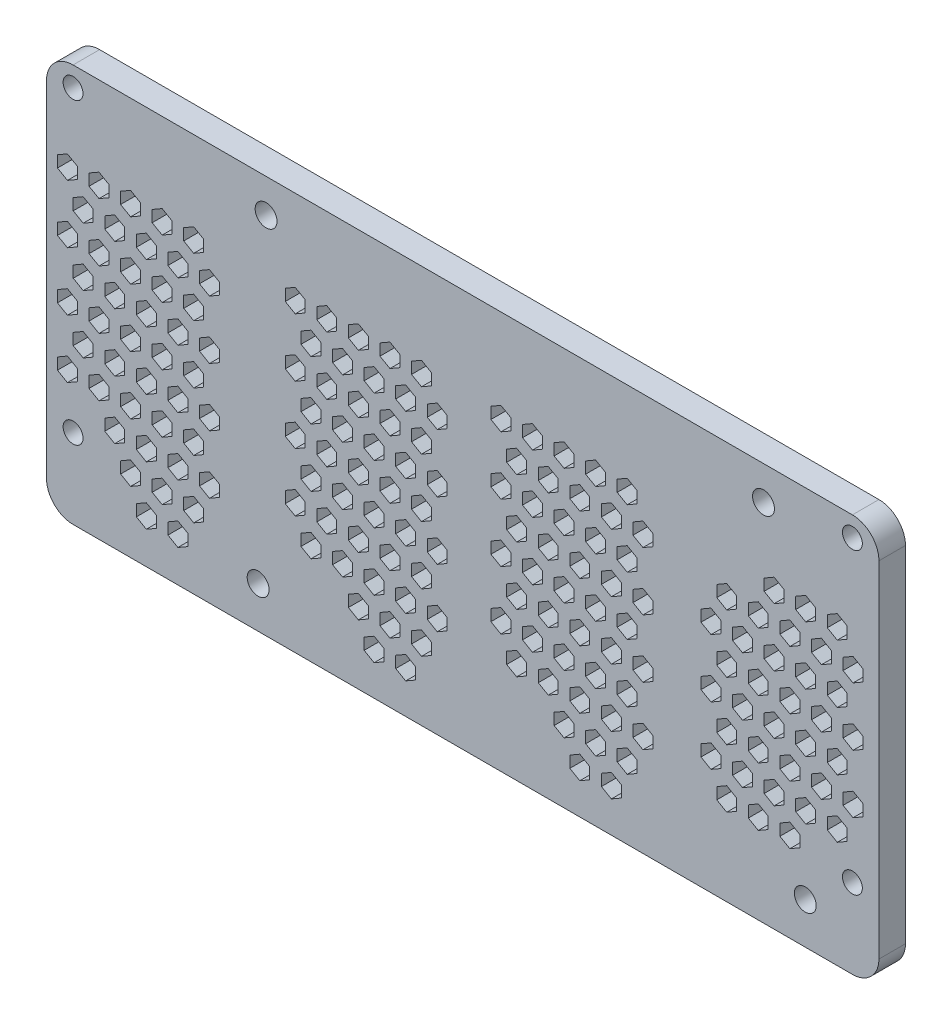
SolidWorks part; units mm, degrees
ref_plane "Front Plane" through (0, 0, 0) normal (0, 0, 1) x (1, 0, 0)
ref_plane "Top Plane" through (0, 0, 0) normal (0, 1, 0) x (1, 0, 0)
ref_plane "Right Plane" through (0, 0, 0) normal (1, 0, 0) x (0, 0, -1)
sketch "Sketch1" plane through (0, 0, 0) normal (0, 0, 1) x (1, 0, 0)
  line L1 (-44, 25.5882) -> (73.5, 25.5882)
  line L2 (-48, 21.5882) -> (-48, -30.4152)
  line L3 (-44, -34.4152) -> (73.5, -34.4152)
  line L4 (77.5, 21.5882) -> (77.5, -30.4152)
  line L10 (-44.8542, 13.5468) -> (-46.3542, 12.6808)
  line L11 (-46.3542, 12.6808) -> (-46.3542, 10.9488)
  line L12 (-46.3542, 10.9488) -> (-44.8542, 10.0827)
  line L13 (-44.8542, 10.0827) -> (-43.3542, 10.9488)
  line L14 (-43.3542, 10.9488) -> (-43.3542, 12.6808)
  line L15 (-43.3542, 12.6808) -> (-44.8542, 13.5468)
  line L17 (-42.4786, 9.1449) -> (-43.9786, 8.2789)
  line L18 (-43.9786, 8.2789) -> (-43.9786, 6.5468)
  line L19 (-43.9786, 6.5468) -> (-42.4786, 5.6808)
  line L20 (-42.4786, 5.6808) -> (-40.9786, 6.5468)
  line L21 (-40.9786, 6.5468) -> (-40.9786, 8.2789)
  line L22 (-40.9786, 8.2789) -> (-42.4786, 9.1449)
  line L23 (-40.0942, 13.5468) -> (-41.5942, 12.6808)
  line L24 (-41.5942, 12.6808) -> (-41.5942, 10.9488)
  line L25 (-41.5942, 10.9488) -> (-40.0942, 10.0827)
  line L26 (-40.0942, 10.0827) -> (-38.5942, 10.9488)
  line L27 (-38.5942, 10.9488) -> (-38.5942, 12.6808)
  line L28 (-38.5942, 12.6808) -> (-40.0942, 13.5468)
  line L29 (-37.7186, 9.1449) -> (-39.2186, 8.2789)
  line L30 (-39.2186, 8.2789) -> (-39.2186, 6.5468)
  line L31 (-39.2186, 6.5468) -> (-37.7186, 5.6808)
  line L32 (-37.7186, 5.6808) -> (-36.2186, 6.5468)
  line L33 (-36.2186, 6.5468) -> (-36.2186, 8.2789)
  line L34 (-36.2186, 8.2789) -> (-37.7186, 9.1449)
  line L35 (-35.3342, 13.5468) -> (-36.8342, 12.6808)
  line L36 (-36.8342, 12.6808) -> (-36.8342, 10.9488)
  line L37 (-36.8342, 10.9488) -> (-35.3342, 10.0827)
  line L38 (-35.3342, 10.0827) -> (-33.8342, 10.9488)
  line L39 (-33.8342, 10.9488) -> (-33.8342, 12.6808)
  line L40 (-33.8342, 12.6808) -> (-35.3342, 13.5468)
  line L41 (-32.9586, 9.1449) -> (-34.4586, 8.2789)
  line L42 (-34.4586, 8.2789) -> (-34.4586, 6.5468)
  line L43 (-34.4586, 6.5468) -> (-32.9586, 5.6808)
  line L44 (-32.9586, 5.6808) -> (-31.4586, 6.5468)
  line L45 (-31.4586, 6.5468) -> (-31.4586, 8.2789)
  line L46 (-31.4586, 8.2789) -> (-32.9586, 9.1449)
  line L47 (-30.5742, 13.5468) -> (-32.0742, 12.6808)
  line L48 (-32.0742, 12.6808) -> (-32.0742, 10.9488)
  line L49 (-32.0742, 10.9488) -> (-30.5742, 10.0827)
  line L50 (-30.5742, 10.0827) -> (-29.0742, 10.9488)
  line L51 (-29.0742, 10.9488) -> (-29.0742, 12.6808)
  line L52 (-29.0742, 12.6808) -> (-30.5742, 13.5468)
  line L53 (-28.1986, 9.1449) -> (-29.6986, 8.2789)
  line L54 (-29.6986, 8.2789) -> (-29.6986, 6.5468)
  line L55 (-29.6986, 6.5468) -> (-28.1986, 5.6808)
  line L56 (-28.1986, 5.6808) -> (-26.6986, 6.5468)
  line L57 (-26.6986, 6.5468) -> (-26.6986, 8.2789)
  line L58 (-26.6986, 8.2789) -> (-28.1986, 9.1449)
  line L59 (-25.8142, 13.5468) -> (-27.3142, 12.6808)
  line L60 (-27.3142, 12.6808) -> (-27.3142, 10.9488)
  line L61 (-27.3142, 10.9488) -> (-25.8142, 10.0827)
  line L62 (-25.8142, 10.0827) -> (-24.3142, 10.9488)
  line L63 (-24.3142, 10.9488) -> (-24.3142, 12.6808)
  line L64 (-24.3142, 12.6808) -> (-25.8142, 13.5468)
  line L65 (-23.4386, 9.1449) -> (-24.9386, 8.2789)
  line L66 (-24.9386, 8.2789) -> (-24.9386, 6.5468)
  line L67 (-24.9386, 6.5468) -> (-23.4386, 5.6808)
  line L68 (-23.4386, 5.6808) -> (-21.9386, 6.5468)
  line L69 (-21.9386, 6.5468) -> (-21.9386, 8.2789)
  line L70 (-21.9386, 8.2789) -> (-23.4386, 9.1449)
  line L71 (-40.0942, 4.7468) -> (-41.5942, 3.8808)
  line L72 (-41.5942, 3.8808) -> (-41.5942, 2.1488)
  line L73 (-41.5942, 2.1488) -> (-40.0942, 1.2827)
  line L74 (-40.0942, 1.2827) -> (-38.5942, 2.1488)
  line L75 (-38.5942, 2.1488) -> (-38.5942, 3.8808)
  line L76 (-38.5942, 3.8808) -> (-40.0942, 4.7468)
  line L77 (-37.7186, 0.3449) -> (-39.2186, -0.5211)
  line L78 (-39.2186, -0.5211) -> (-39.2186, -2.2532)
  line L79 (-39.2186, -2.2532) -> (-37.7186, -3.1192)
  line L80 (-37.7186, -3.1192) -> (-36.2186, -2.2532)
  line L81 (-36.2186, -2.2532) -> (-36.2186, -0.5211)
  line L82 (-36.2186, -0.5211) -> (-37.7186, 0.3449)
  line L83 (-35.3342, 4.7468) -> (-36.8342, 3.8808)
  line L84 (-36.8342, 3.8808) -> (-36.8342, 2.1488)
  line L85 (-36.8342, 2.1488) -> (-35.3342, 1.2827)
  line L86 (-35.3342, 1.2827) -> (-33.8342, 2.1488)
  line L87 (-33.8342, 2.1488) -> (-33.8342, 3.8808)
  line L88 (-33.8342, 3.8808) -> (-35.3342, 4.7468)
  line L89 (-32.9586, 0.3449) -> (-34.4586, -0.5211)
  line L90 (-34.4586, -0.5211) -> (-34.4586, -2.2532)
  line L91 (-34.4586, -2.2532) -> (-32.9586, -3.1192)
  line L92 (-32.9586, -3.1192) -> (-31.4586, -2.2532)
  line L93 (-31.4586, -2.2532) -> (-31.4586, -0.5211)
  line L94 (-31.4586, -0.5211) -> (-32.9586, 0.3449)
  line L95 (-30.5742, 4.7468) -> (-32.0742, 3.8808)
  line L96 (-32.0742, 3.8808) -> (-32.0742, 2.1488)
  line L97 (-32.0742, 2.1488) -> (-30.5742, 1.2827)
  line L98 (-30.5742, 1.2827) -> (-29.0742, 2.1488)
  line L99 (-29.0742, 2.1488) -> (-29.0742, 3.8808)
  line L100 (-29.0742, 3.8808) -> (-30.5742, 4.7468)
  line L101 (-28.1986, 0.3449) -> (-29.6986, -0.5211)
  line L102 (-29.6986, -0.5211) -> (-29.6986, -2.2532)
  line L103 (-29.6986, -2.2532) -> (-28.1986, -3.1192)
  line L104 (-28.1986, -3.1192) -> (-26.6986, -2.2532)
  line L105 (-26.6986, -2.2532) -> (-26.6986, -0.5211)
  line L106 (-26.6986, -0.5211) -> (-28.1986, 0.3449)
  line L107 (-25.8142, 4.7468) -> (-27.3142, 3.8808)
  line L108 (-27.3142, 3.8808) -> (-27.3142, 2.1488)
  line L109 (-27.3142, 2.1488) -> (-25.8142, 1.2827)
  line L110 (-25.8142, 1.2827) -> (-24.3142, 2.1488)
  line L111 (-24.3142, 2.1488) -> (-24.3142, 3.8808)
  line L112 (-24.3142, 3.8808) -> (-25.8142, 4.7468)
  line L113 (-23.4386, 0.3449) -> (-24.9386, -0.5211)
  line L114 (-24.9386, -0.5211) -> (-24.9386, -2.2532)
  line L115 (-24.9386, -2.2532) -> (-23.4386, -3.1192)
  line L116 (-23.4386, -3.1192) -> (-21.9386, -2.2532)
  line L117 (-21.9386, -2.2532) -> (-21.9386, -0.5211)
  line L118 (-21.9386, -0.5211) -> (-23.4386, 0.3449)
  line L119 (-40.0942, -4.0532) -> (-41.5942, -4.9192)
  line L120 (-41.5942, -4.9192) -> (-41.5942, -6.6512)
  line L121 (-41.5942, -6.6512) -> (-40.0942, -7.5173)
  line L122 (-40.0942, -7.5173) -> (-38.5942, -6.6512)
  line L123 (-38.5942, -6.6512) -> (-38.5942, -4.9192)
  line L124 (-38.5942, -4.9192) -> (-40.0942, -4.0532)
  line L125 (-37.7186, -8.4551) -> (-39.2186, -9.3211)
  line L126 (-39.2186, -9.3211) -> (-39.2186, -11.0532)
  line L127 (-39.2186, -11.0532) -> (-37.7186, -11.9192)
  line L128 (-37.7186, -11.9192) -> (-36.2186, -11.0532)
  line L129 (-36.2186, -11.0532) -> (-36.2186, -9.3211)
  line L130 (-36.2186, -9.3211) -> (-37.7186, -8.4551)
  line L131 (-35.3342, -4.0532) -> (-36.8342, -4.9192)
  line L132 (-36.8342, -4.9192) -> (-36.8342, -6.6512)
  line L133 (-36.8342, -6.6512) -> (-35.3342, -7.5173)
  line L134 (-35.3342, -7.5173) -> (-33.8342, -6.6512)
  line L135 (-33.8342, -6.6512) -> (-33.8342, -4.9192)
  line L136 (-33.8342, -4.9192) -> (-35.3342, -4.0532)
  line L137 (-32.9586, -8.4551) -> (-34.4586, -9.3211)
  line L138 (-34.4586, -9.3211) -> (-34.4586, -11.0532)
  line L139 (-34.4586, -11.0532) -> (-32.9586, -11.9192)
  line L140 (-32.9586, -11.9192) -> (-31.4586, -11.0532)
  line L141 (-31.4586, -11.0532) -> (-31.4586, -9.3211)
  line L142 (-31.4586, -9.3211) -> (-32.9586, -8.4551)
  line L143 (-30.5742, -4.0532) -> (-32.0742, -4.9192)
  line L144 (-32.0742, -4.9192) -> (-32.0742, -6.6512)
  line L145 (-32.0742, -6.6512) -> (-30.5742, -7.5173)
  line L146 (-30.5742, -7.5173) -> (-29.0742, -6.6512)
  line L147 (-29.0742, -6.6512) -> (-29.0742, -4.9192)
  line L148 (-29.0742, -4.9192) -> (-30.5742, -4.0532)
  line L149 (-28.1986, -8.4551) -> (-29.6986, -9.3211)
  line L150 (-29.6986, -9.3211) -> (-29.6986, -11.0532)
  line L151 (-29.6986, -11.0532) -> (-28.1986, -11.9192)
  line L152 (-28.1986, -11.9192) -> (-26.6986, -11.0532)
  line L153 (-26.6986, -11.0532) -> (-26.6986, -9.3211)
  line L154 (-26.6986, -9.3211) -> (-28.1986, -8.4551)
  line L155 (-25.8142, -4.0532) -> (-27.3142, -4.9192)
  line L156 (-27.3142, -4.9192) -> (-27.3142, -6.6512)
  line L157 (-27.3142, -6.6512) -> (-25.8142, -7.5173)
  line L158 (-25.8142, -7.5173) -> (-24.3142, -6.6512)
  line L159 (-24.3142, -6.6512) -> (-24.3142, -4.9192)
  line L160 (-24.3142, -4.9192) -> (-25.8142, -4.0532)
  line L161 (-23.4386, -8.4551) -> (-24.9386, -9.3211)
  line L162 (-24.9386, -9.3211) -> (-24.9386, -11.0532)
  line L163 (-24.9386, -11.0532) -> (-23.4386, -11.9192)
  line L164 (-23.4386, -11.9192) -> (-21.9386, -11.0532)
  line L165 (-21.9386, -11.0532) -> (-21.9386, -9.3211)
  line L166 (-21.9386, -9.3211) -> (-23.4386, -8.4551)
  line L167 (-40.0942, -12.8532) -> (-41.5942, -13.7192)
  line L168 (-41.5942, -13.7192) -> (-41.5942, -15.4512)
  line L169 (-41.5942, -15.4512) -> (-40.0942, -16.3173)
  line L170 (-40.0942, -16.3173) -> (-38.5942, -15.4512)
  line L171 (-38.5942, -15.4512) -> (-38.5942, -13.7192)
  line L172 (-38.5942, -13.7192) -> (-40.0942, -12.8532)
  line L173 (-37.7186, -17.2551) -> (-39.2186, -18.1211)
  line L174 (-39.2186, -18.1211) -> (-39.2186, -19.8532)
  line L175 (-39.2186, -19.8532) -> (-37.7186, -20.7192)
  line L176 (-37.7186, -20.7192) -> (-36.2186, -19.8532)
  line L177 (-36.2186, -19.8532) -> (-36.2186, -18.1211)
  line L178 (-36.2186, -18.1211) -> (-37.7186, -17.2551)
  line L179 (-35.3342, -12.8532) -> (-36.8342, -13.7192)
  line L180 (-36.8342, -13.7192) -> (-36.8342, -15.4512)
  line L181 (-36.8342, -15.4512) -> (-35.3342, -16.3173)
  line L182 (-35.3342, -16.3173) -> (-33.8342, -15.4512)
  line L183 (-33.8342, -15.4512) -> (-33.8342, -13.7192)
  line L184 (-33.8342, -13.7192) -> (-35.3342, -12.8532)
  line L185 (-32.9586, -17.2551) -> (-34.4586, -18.1211)
  line L186 (-34.4586, -18.1211) -> (-34.4586, -19.8532)
  line L187 (-34.4586, -19.8532) -> (-32.9586, -20.7192)
  line L188 (-32.9586, -20.7192) -> (-31.4586, -19.8532)
  line L189 (-31.4586, -19.8532) -> (-31.4586, -18.1211)
  line L190 (-31.4586, -18.1211) -> (-32.9586, -17.2551)
  line L191 (-30.5742, -12.8532) -> (-32.0742, -13.7192)
  line L192 (-32.0742, -13.7192) -> (-32.0742, -15.4512)
  line L193 (-32.0742, -15.4512) -> (-30.5742, -16.3173)
  line L194 (-30.5742, -16.3173) -> (-29.0742, -15.4512)
  line L195 (-29.0742, -15.4512) -> (-29.0742, -13.7192)
  line L196 (-29.0742, -13.7192) -> (-30.5742, -12.8532)
  line L197 (-28.1986, -17.2551) -> (-29.6986, -18.1211)
  line L198 (-29.6986, -18.1211) -> (-29.6986, -19.8532)
  line L199 (-29.6986, -19.8532) -> (-28.1986, -20.7192)
  line L200 (-28.1986, -20.7192) -> (-26.6986, -19.8532)
  line L201 (-26.6986, -19.8532) -> (-26.6986, -18.1211)
  line L202 (-26.6986, -18.1211) -> (-28.1986, -17.2551)
  line L203 (-25.8142, -12.8532) -> (-27.3142, -13.7192)
  line L204 (-27.3142, -13.7192) -> (-27.3142, -15.4512)
  line L205 (-27.3142, -15.4512) -> (-25.8142, -16.3173)
  line L206 (-25.8142, -16.3173) -> (-24.3142, -15.4512)
  line L207 (-24.3142, -15.4512) -> (-24.3142, -13.7192)
  line L208 (-24.3142, -13.7192) -> (-25.8142, -12.8532)
  line L209 (-23.4386, -17.2551) -> (-24.9386, -18.1211)
  line L210 (-24.9386, -18.1211) -> (-24.9386, -19.8532)
  line L211 (-24.9386, -19.8532) -> (-23.4386, -20.7192)
  line L212 (-23.4386, -20.7192) -> (-21.9386, -19.8532)
  line L213 (-21.9386, -19.8532) -> (-21.9386, -18.1211)
  line L214 (-21.9386, -18.1211) -> (-23.4386, -17.2551)
  line L227 (-35.3342, -21.6532) -> (-36.8342, -22.5192)
  line L228 (-36.8342, -22.5192) -> (-36.8342, -24.2512)
  line L229 (-36.8342, -24.2512) -> (-35.3342, -25.1173)
  line L230 (-35.3342, -25.1173) -> (-33.8342, -24.2512)
  line L231 (-33.8342, -24.2512) -> (-33.8342, -22.5192)
  line L232 (-33.8342, -22.5192) -> (-35.3342, -21.6532)
  line L233 (-32.9586, -26.0551) -> (-34.4586, -26.9211)
  line L234 (-34.4586, -26.9211) -> (-34.4586, -28.6532)
  line L235 (-34.4586, -28.6532) -> (-32.9586, -29.5192)
  line L236 (-32.9586, -29.5192) -> (-31.4586, -28.6532)
  line L237 (-31.4586, -28.6532) -> (-31.4586, -26.9211)
  line L238 (-31.4586, -26.9211) -> (-32.9586, -26.0551)
  line L239 (-30.5742, -21.6532) -> (-32.0742, -22.5192)
  line L240 (-32.0742, -22.5192) -> (-32.0742, -24.2512)
  line L241 (-32.0742, -24.2512) -> (-30.5742, -25.1173)
  line L242 (-30.5742, -25.1173) -> (-29.0742, -24.2512)
  line L243 (-29.0742, -24.2512) -> (-29.0742, -22.5192)
  line L244 (-29.0742, -22.5192) -> (-30.5742, -21.6532)
  line L245 (-28.1986, -26.0551) -> (-29.6986, -26.9211)
  line L246 (-29.6986, -26.9211) -> (-29.6986, -28.6532)
  line L247 (-29.6986, -28.6532) -> (-28.1986, -29.5192)
  line L248 (-28.1986, -29.5192) -> (-26.6986, -28.6532)
  line L249 (-26.6986, -28.6532) -> (-26.6986, -26.9211)
  line L250 (-26.6986, -26.9211) -> (-28.1986, -26.0551)
  line L251 (-25.8142, -21.6532) -> (-27.3142, -22.5192)
  line L252 (-27.3142, -22.5192) -> (-27.3142, -24.2512)
  line L253 (-27.3142, -24.2512) -> (-25.8142, -25.1173)
  line L254 (-25.8142, -25.1173) -> (-24.3142, -24.2512)
  line L255 (-24.3142, -24.2512) -> (-24.3142, -22.5192)
  line L256 (-24.3142, -22.5192) -> (-25.8142, -21.6532)
  line L263 (-44.8542, 4.7468) -> (-46.3542, 3.8808)
  line L264 (-46.3542, 3.8808) -> (-46.3542, 2.1488)
  line L265 (-46.3542, 2.1488) -> (-44.8542, 1.2827)
  line L266 (-44.8542, 1.2827) -> (-43.3542, 2.1488)
  line L267 (-43.3542, 2.1488) -> (-43.3542, 3.8808)
  line L268 (-43.3542, 3.8808) -> (-44.8542, 4.7468)
  line L269 (-42.4786, 0.3449) -> (-43.9786, -0.5211)
  line L270 (-43.9786, -0.5211) -> (-43.9786, -2.2532)
  line L271 (-43.9786, -2.2532) -> (-42.4786, -3.1192)
  line L272 (-42.4786, -3.1192) -> (-40.9786, -2.2532)
  line L273 (-40.9786, -2.2532) -> (-40.9786, -0.5211)
  line L274 (-40.9786, -0.5211) -> (-42.4786, 0.3449)
  line L275 (-44.8542, -4.0532) -> (-46.3542, -4.9192)
  line L276 (-46.3542, -4.9192) -> (-46.3542, -6.6512)
  line L277 (-46.3542, -6.6512) -> (-44.8542, -7.5173)
  line L278 (-44.8542, -7.5173) -> (-43.3542, -6.6512)
  line L279 (-43.3542, -6.6512) -> (-43.3542, -4.9192)
  line L280 (-43.3542, -4.9192) -> (-44.8542, -4.0532)
  line L281 (-42.4786, -8.4551) -> (-43.9786, -9.3211)
  line L282 (-43.9786, -9.3211) -> (-43.9786, -11.0532)
  line L283 (-43.9786, -11.0532) -> (-42.4786, -11.9192)
  line L284 (-42.4786, -11.9192) -> (-40.9786, -11.0532)
  line L285 (-40.9786, -11.0532) -> (-40.9786, -9.3211)
  line L286 (-40.9786, -9.3211) -> (-42.4786, -8.4551)
  line L287 (-44.8542, -12.8532) -> (-46.3542, -13.7192)
  line L288 (-46.3542, -13.7192) -> (-46.3542, -15.4512)
  line L289 (-46.3542, -15.4512) -> (-44.8542, -16.3173)
  line L290 (-44.8542, -16.3173) -> (-43.3542, -15.4512)
  line L291 (-43.3542, -15.4512) -> (-43.3542, -13.7192)
  line L292 (-43.3542, -13.7192) -> (-44.8542, -12.8532)
  line L311 (-44.8542, -21.6532) -> (-46.3542, -22.5192) [skipped]
  line L312 (-46.3542, -22.5192) -> (-46.3542, -24.2512) [skipped]
  line L313 (-46.3542, -24.2512) -> (-44.8542, -25.1173) [skipped]
  line L314 (-44.8542, -25.1173) -> (-43.3542, -24.2512) [skipped]
  line L315 (-43.3542, -24.2512) -> (-43.3542, -22.5192) [skipped]
  line L316 (-43.3542, -22.5192) -> (-44.8542, -21.6532) [skipped]
  line L317 (-42.4786, -26.0551) -> (-43.9786, -26.9211) [skipped]
  line L318 (-43.9786, -26.9211) -> (-43.9786, -28.6532) [skipped]
  line L319 (-43.9786, -28.6532) -> (-42.4786, -29.5192) [skipped]
  line L320 (-42.4786, -29.5192) -> (-40.9786, -28.6532) [skipped]
  line L321 (-40.9786, -28.6532) -> (-40.9786, -26.9211) [skipped]
  line L322 (-40.9786, -26.9211) -> (-42.4786, -26.0551) [skipped]
  line L323 (-37.7186, -26.0551) -> (-39.2186, -26.9211) [skipped]
  line L324 (-39.2186, -26.9211) -> (-39.2186, -28.6532) [skipped]
  line L325 (-39.2186, -28.6532) -> (-37.7186, -29.5192) [skipped]
  line L326 (-37.7186, -29.5192) -> (-36.2186, -28.6532) [skipped]
  line L327 (-36.2186, -28.6532) -> (-36.2186, -26.9211) [skipped]
  line L328 (-36.2186, -26.9211) -> (-37.7186, -26.0551) [skipped]
  line L329 (-40.0942, -21.6532) -> (-41.5942, -22.5192) [skipped]
  line L330 (-41.5942, -22.5192) -> (-41.5942, -24.2512) [skipped]
  line L331 (-41.5942, -24.2512) -> (-40.0942, -25.1173) [skipped]
  line L332 (-40.0942, -25.1173) -> (-38.5942, -24.2512) [skipped]
  line L333 (-38.5942, -24.2512) -> (-38.5942, -22.5192) [skipped]
  line L334 (-38.5942, -22.5192) -> (-40.0942, -21.6532) [skipped]
  line L335 (-23.4386, -26.0551) -> (-24.9386, -26.9211) [skipped]
  line L336 (-24.9386, -26.9211) -> (-24.9386, -28.6532) [skipped]
  line L337 (-24.9386, -28.6532) -> (-23.4386, -29.5192) [skipped]
  line L338 (-23.4386, -29.5192) -> (-21.9386, -28.6532) [skipped]
  line L339 (-21.9386, -28.6532) -> (-21.9386, -26.9211) [skipped]
  line L340 (-21.9386, -26.9211) -> (-23.4386, -26.0551) [skipped]
  line L347 (54.5534, 7.152) -> (53.0534, 6.286)
  line L348 (53.0534, 6.286) -> (53.0534, 4.554)
  line L349 (53.0534, 4.554) -> (54.5534, 3.6879)
  line L350 (54.5534, 3.6879) -> (56.0534, 4.554)
  line L351 (56.0534, 4.554) -> (56.0534, 6.286)
  line L352 (56.0534, 6.286) -> (54.5534, 7.152)
  line L359 (59.3134, 7.152) -> (57.8134, 6.286)
  line L360 (57.8134, 6.286) -> (57.8134, 4.554)
  line L361 (57.8134, 4.554) -> (59.3134, 3.6879)
  line L362 (59.3134, 3.6879) -> (60.8134, 4.554)
  line L363 (60.8134, 4.554) -> (60.8134, 6.286)
  line L364 (60.8134, 6.286) -> (59.3134, 7.152)
  line L365 (61.6978, 11.554) -> (60.1978, 10.6879)
  line L366 (60.1978, 10.6879) -> (60.1978, 8.9559)
  line L367 (60.1978, 8.9559) -> (61.6978, 8.0899)
  line L368 (61.6978, 8.0899) -> (63.1978, 8.9559)
  line L369 (63.1978, 8.9559) -> (63.1978, 10.6879)
  line L370 (63.1978, 10.6879) -> (61.6978, 11.554)
  line L371 (64.0734, 7.152) -> (62.5734, 6.286)
  line L372 (62.5734, 6.286) -> (62.5734, 4.554)
  line L373 (62.5734, 4.554) -> (64.0734, 3.6879)
  line L374 (64.0734, 3.6879) -> (65.5734, 4.554)
  line L375 (65.5734, 4.554) -> (65.5734, 6.286)
  line L376 (65.5734, 6.286) -> (64.0734, 7.152)
  line L377 (66.4578, 11.554) -> (64.9578, 10.6879)
  line L378 (64.9578, 10.6879) -> (64.9578, 8.9559)
  line L379 (64.9578, 8.9559) -> (66.4578, 8.0899)
  line L380 (66.4578, 8.0899) -> (67.9578, 8.9559)
  line L381 (67.9578, 8.9559) -> (67.9578, 10.6879)
  line L382 (67.9578, 10.6879) -> (66.4578, 11.554)
  line L383 (68.8334, 7.152) -> (67.3334, 6.286)
  line L384 (67.3334, 6.286) -> (67.3334, 4.554)
  line L385 (67.3334, 4.554) -> (68.8334, 3.6879)
  line L386 (68.8334, 3.6879) -> (70.3334, 4.554)
  line L387 (70.3334, 4.554) -> (70.3334, 6.286)
  line L388 (70.3334, 6.286) -> (68.8334, 7.152)
  line L389 (71.2178, 11.554) -> (69.7178, 10.6879)
  line L390 (69.7178, 10.6879) -> (69.7178, 8.9559)
  line L391 (69.7178, 8.9559) -> (71.2178, 8.0899)
  line L392 (71.2178, 8.0899) -> (72.7178, 8.9559)
  line L393 (72.7178, 8.9559) -> (72.7178, 10.6879)
  line L394 (72.7178, 10.6879) -> (71.2178, 11.554)
  line L395 (73.5934, 7.152) -> (72.0934, 6.286)
  line L396 (72.0934, 6.286) -> (72.0934, 4.554)
  line L397 (72.0934, 4.554) -> (73.5934, 3.6879)
  line L398 (73.5934, 3.6879) -> (75.0934, 4.554)
  line L399 (75.0934, 4.554) -> (75.0934, 6.286)
  line L400 (75.0934, 6.286) -> (73.5934, 7.152)
  line L401 (56.9378, 2.754) -> (55.4378, 1.8879)
  line L402 (55.4378, 1.8879) -> (55.4378, 0.1559)
  line L403 (55.4378, 0.1559) -> (56.9378, -0.7101)
  line L404 (56.9378, -0.7101) -> (58.4378, 0.1559)
  line L405 (58.4378, 0.1559) -> (58.4378, 1.8879)
  line L406 (58.4378, 1.8879) -> (56.9378, 2.754)
  line L407 (59.3134, -1.648) -> (57.8134, -2.514)
  line L408 (57.8134, -2.514) -> (57.8134, -4.246)
  line L409 (57.8134, -4.246) -> (59.3134, -5.1121)
  line L410 (59.3134, -5.1121) -> (60.8134, -4.246)
  line L411 (60.8134, -4.246) -> (60.8134, -2.514)
  line L412 (60.8134, -2.514) -> (59.3134, -1.648)
  line L413 (61.6978, 2.754) -> (60.1978, 1.8879)
  line L414 (60.1978, 1.8879) -> (60.1978, 0.1559)
  line L415 (60.1978, 0.1559) -> (61.6978, -0.7101)
  line L416 (61.6978, -0.7101) -> (63.1978, 0.1559)
  line L417 (63.1978, 0.1559) -> (63.1978, 1.8879)
  line L418 (63.1978, 1.8879) -> (61.6978, 2.754)
  line L419 (64.0734, -1.648) -> (62.5734, -2.514)
  line L420 (62.5734, -2.514) -> (62.5734, -4.246)
  line L421 (62.5734, -4.246) -> (64.0734, -5.1121)
  line L422 (64.0734, -5.1121) -> (65.5734, -4.246)
  line L423 (65.5734, -4.246) -> (65.5734, -2.514)
  line L424 (65.5734, -2.514) -> (64.0734, -1.648)
  line L425 (66.4578, 2.754) -> (64.9578, 1.8879)
  line L426 (64.9578, 1.8879) -> (64.9578, 0.1559)
  line L427 (64.9578, 0.1559) -> (66.4578, -0.7101)
  line L428 (66.4578, -0.7101) -> (67.9578, 0.1559)
  line L429 (67.9578, 0.1559) -> (67.9578, 1.8879)
  line L430 (67.9578, 1.8879) -> (66.4578, 2.754)
  line L431 (68.8334, -1.648) -> (67.3334, -2.514)
  line L432 (67.3334, -2.514) -> (67.3334, -4.246)
  line L433 (67.3334, -4.246) -> (68.8334, -5.1121)
  line L434 (68.8334, -5.1121) -> (70.3334, -4.246)
  line L435 (70.3334, -4.246) -> (70.3334, -2.514)
  line L436 (70.3334, -2.514) -> (68.8334, -1.648)
  line L437 (71.2178, 2.754) -> (69.7178, 1.8879)
  line L438 (69.7178, 1.8879) -> (69.7178, 0.1559)
  line L439 (69.7178, 0.1559) -> (71.2178, -0.7101)
  line L440 (71.2178, -0.7101) -> (72.7178, 0.1559)
  line L441 (72.7178, 0.1559) -> (72.7178, 1.8879)
  line L442 (72.7178, 1.8879) -> (71.2178, 2.754)
  line L443 (73.5934, -1.648) -> (72.0934, -2.514)
  line L444 (72.0934, -2.514) -> (72.0934, -4.246)
  line L445 (72.0934, -4.246) -> (73.5934, -5.1121)
  line L446 (73.5934, -5.1121) -> (75.0934, -4.246)
  line L447 (75.0934, -4.246) -> (75.0934, -2.514)
  line L448 (75.0934, -2.514) -> (73.5934, -1.648)
  line L449 (56.9378, -6.046) -> (55.4378, -6.9121)
  line L450 (55.4378, -6.9121) -> (55.4378, -8.6441)
  line L451 (55.4378, -8.6441) -> (56.9378, -9.5101)
  line L452 (56.9378, -9.5101) -> (58.4378, -8.6441)
  line L453 (58.4378, -8.6441) -> (58.4378, -6.9121)
  line L454 (58.4378, -6.9121) -> (56.9378, -6.046)
  line L455 (59.3134, -10.448) -> (57.8134, -11.314)
  line L456 (57.8134, -11.314) -> (57.8134, -13.046)
  line L457 (57.8134, -13.046) -> (59.3134, -13.9121)
  line L458 (59.3134, -13.9121) -> (60.8134, -13.046)
  line L459 (60.8134, -13.046) -> (60.8134, -11.314)
  line L460 (60.8134, -11.314) -> (59.3134, -10.448)
  line L461 (61.6978, -6.046) -> (60.1978, -6.9121)
  line L462 (60.1978, -6.9121) -> (60.1978, -8.6441)
  line L463 (60.1978, -8.6441) -> (61.6978, -9.5101)
  line L464 (61.6978, -9.5101) -> (63.1978, -8.6441)
  line L465 (63.1978, -8.6441) -> (63.1978, -6.9121)
  line L466 (63.1978, -6.9121) -> (61.6978, -6.046)
  line L467 (64.0734, -10.448) -> (62.5734, -11.314)
  line L468 (62.5734, -11.314) -> (62.5734, -13.046)
  line L469 (62.5734, -13.046) -> (64.0734, -13.9121)
  line L470 (64.0734, -13.9121) -> (65.5734, -13.046)
  line L471 (65.5734, -13.046) -> (65.5734, -11.314)
  line L472 (65.5734, -11.314) -> (64.0734, -10.448)
  line L473 (66.4578, -6.046) -> (64.9578, -6.9121)
  line L474 (64.9578, -6.9121) -> (64.9578, -8.6441)
  line L475 (64.9578, -8.6441) -> (66.4578, -9.5101)
  line L476 (66.4578, -9.5101) -> (67.9578, -8.6441)
  line L477 (67.9578, -8.6441) -> (67.9578, -6.9121)
  line L478 (67.9578, -6.9121) -> (66.4578, -6.046)
  line L479 (68.8334, -10.448) -> (67.3334, -11.314)
  line L480 (67.3334, -11.314) -> (67.3334, -13.046)
  line L481 (67.3334, -13.046) -> (68.8334, -13.9121)
  line L482 (68.8334, -13.9121) -> (70.3334, -13.046)
  line L483 (70.3334, -13.046) -> (70.3334, -11.314)
  line L484 (70.3334, -11.314) -> (68.8334, -10.448)
  line L485 (71.2178, -6.046) -> (69.7178, -6.9121)
  line L486 (69.7178, -6.9121) -> (69.7178, -8.6441)
  line L487 (69.7178, -8.6441) -> (71.2178, -9.5101)
  line L488 (71.2178, -9.5101) -> (72.7178, -8.6441)
  line L489 (72.7178, -8.6441) -> (72.7178, -6.9121)
  line L490 (72.7178, -6.9121) -> (71.2178, -6.046)
  line L491 (73.5934, -10.448) -> (72.0934, -11.314)
  line L492 (72.0934, -11.314) -> (72.0934, -13.046)
  line L493 (72.0934, -13.046) -> (73.5934, -13.9121)
  line L494 (73.5934, -13.9121) -> (75.0934, -13.046)
  line L495 (75.0934, -13.046) -> (75.0934, -11.314)
  line L496 (75.0934, -11.314) -> (73.5934, -10.448)
  line L497 (56.9378, -14.846) -> (55.4378, -15.7121)
  line L498 (55.4378, -15.7121) -> (55.4378, -17.4441)
  line L499 (55.4378, -17.4441) -> (56.9378, -18.3101)
  line L500 (56.9378, -18.3101) -> (58.4378, -17.4441)
  line L501 (58.4378, -17.4441) -> (58.4378, -15.7121)
  line L502 (58.4378, -15.7121) -> (56.9378, -14.846)
  line L503 (59.3134, -19.248) -> (57.8134, -20.114)
  line L504 (57.8134, -20.114) -> (57.8134, -21.846)
  line L505 (57.8134, -21.846) -> (59.3134, -22.7121)
  line L506 (59.3134, -22.7121) -> (60.8134, -21.846)
  line L507 (60.8134, -21.846) -> (60.8134, -20.114)
  line L508 (60.8134, -20.114) -> (59.3134, -19.248)
  line L509 (61.6978, -14.846) -> (60.1978, -15.7121)
  line L510 (60.1978, -15.7121) -> (60.1978, -17.4441)
  line L511 (60.1978, -17.4441) -> (61.6978, -18.3101)
  line L512 (61.6978, -18.3101) -> (63.1978, -17.4441)
  line L513 (63.1978, -17.4441) -> (63.1978, -15.7121)
  line L514 (63.1978, -15.7121) -> (61.6978, -14.846)
  line L515 (64.0734, -19.248) -> (62.5734, -20.114)
  line L516 (62.5734, -20.114) -> (62.5734, -21.846)
  line L517 (62.5734, -21.846) -> (64.0734, -22.7121)
  line L518 (64.0734, -22.7121) -> (65.5734, -21.846)
  line L519 (65.5734, -21.846) -> (65.5734, -20.114)
  line L520 (65.5734, -20.114) -> (64.0734, -19.248)
  line L521 (66.4578, -14.846) -> (64.9578, -15.7121)
  line L522 (64.9578, -15.7121) -> (64.9578, -17.4441)
  line L523 (64.9578, -17.4441) -> (66.4578, -18.3101)
  line L524 (66.4578, -18.3101) -> (67.9578, -17.4441)
  line L525 (67.9578, -17.4441) -> (67.9578, -15.7121)
  line L526 (67.9578, -15.7121) -> (66.4578, -14.846)
  line L533 (71.2178, -14.846) -> (69.7178, -15.7121)
  line L534 (69.7178, -15.7121) -> (69.7178, -17.4441)
  line L535 (69.7178, -17.4441) -> (71.2178, -18.3101)
  line L536 (71.2178, -18.3101) -> (72.7178, -17.4441)
  line L537 (72.7178, -17.4441) -> (72.7178, -15.7121)
  line L538 (72.7178, -15.7121) -> (71.2178, -14.846)
  line L575 (52.1778, 2.754) -> (50.6778, 1.8879)
  line L576 (50.6778, 1.8879) -> (50.6778, 0.1559)
  line L577 (50.6778, 0.1559) -> (52.1778, -0.7101)
  line L578 (52.1778, -0.7101) -> (53.6778, 0.1559)
  line L579 (53.6778, 0.1559) -> (53.6778, 1.8879)
  line L580 (53.6778, 1.8879) -> (52.1778, 2.754)
  line L581 (54.5534, -1.648) -> (53.0534, -2.514)
  line L582 (53.0534, -2.514) -> (53.0534, -4.246)
  line L583 (53.0534, -4.246) -> (54.5534, -5.1121)
  line L584 (54.5534, -5.1121) -> (56.0534, -4.246)
  line L585 (56.0534, -4.246) -> (56.0534, -2.514)
  line L586 (56.0534, -2.514) -> (54.5534, -1.648)
  line L587 (52.1778, -6.046) -> (50.6778, -6.9121)
  line L588 (50.6778, -6.9121) -> (50.6778, -8.6441)
  line L589 (50.6778, -8.6441) -> (52.1778, -9.5101)
  line L590 (52.1778, -9.5101) -> (53.6778, -8.6441)
  line L591 (53.6778, -8.6441) -> (53.6778, -6.9121)
  line L592 (53.6778, -6.9121) -> (52.1778, -6.046)
  line L593 (54.5534, -10.448) -> (53.0534, -11.314)
  line L594 (53.0534, -11.314) -> (53.0534, -13.046)
  line L595 (53.0534, -13.046) -> (54.5534, -13.9121)
  line L596 (54.5534, -13.9121) -> (56.0534, -13.046)
  line L597 (56.0534, -13.046) -> (56.0534, -11.314)
  line L598 (56.0534, -11.314) -> (54.5534, -10.448)
  line L599 (52.1778, -14.846) -> (50.6778, -15.7121)
  line L600 (50.6778, -15.7121) -> (50.6778, -17.4441)
  line L601 (50.6778, -17.4441) -> (52.1778, -18.3101)
  line L602 (52.1778, -18.3101) -> (53.6778, -17.4441)
  line L603 (53.6778, -17.4441) -> (53.6778, -15.7121)
  line L604 (53.6778, -15.7121) -> (52.1778, -14.846)
  line L605 (54.5534, -19.248) -> (53.0534, -20.114)
  line L606 (53.0534, -20.114) -> (53.0534, -21.846)
  line L607 (53.0534, -21.846) -> (54.5534, -22.7121)
  line L608 (54.5534, -22.7121) -> (56.0534, -21.846)
  line L609 (56.0534, -21.846) -> (56.0534, -20.114)
  line L610 (56.0534, -20.114) -> (54.5534, -19.248)
  line L611 (-10.5093, 13.2923) -> (-12.0093, 12.4263)
  line L612 (-12.0093, 12.4263) -> (-12.0093, 10.6942)
  line L613 (-12.0093, 10.6942) -> (-10.5093, 9.8282)
  line L614 (-10.5093, 9.8282) -> (-9.0093, 10.6942)
  line L615 (-9.0093, 10.6942) -> (-9.0093, 12.4263)
  line L616 (-9.0093, 12.4263) -> (-10.5093, 13.2923)
  line L617 (-8.1336, 8.8904) -> (-9.6336, 8.0244)
  line L618 (-9.6336, 8.0244) -> (-9.6336, 6.2923)
  line L619 (-9.6336, 6.2923) -> (-8.1336, 5.4263)
  line L620 (-8.1336, 5.4263) -> (-6.6336, 6.2923)
  line L621 (-6.6336, 6.2923) -> (-6.6336, 8.0244)
  line L622 (-6.6336, 8.0244) -> (-8.1336, 8.8904)
  line L623 (-5.7493, 13.2923) -> (-7.2493, 12.4263)
  line L624 (-7.2493, 12.4263) -> (-7.2493, 10.6942)
  line L625 (-7.2493, 10.6942) -> (-5.7493, 9.8282)
  line L626 (-5.7493, 9.8282) -> (-4.2493, 10.6942)
  line L627 (-4.2493, 10.6942) -> (-4.2493, 12.4263)
  line L628 (-4.2493, 12.4263) -> (-5.7493, 13.2923)
  line L629 (-3.3736, 8.8904) -> (-4.8736, 8.0244)
  line L630 (-4.8736, 8.0244) -> (-4.8736, 6.2923)
  line L631 (-4.8736, 6.2923) -> (-3.3736, 5.4263)
  line L632 (-3.3736, 5.4263) -> (-1.8736, 6.2923)
  line L633 (-1.8736, 6.2923) -> (-1.8736, 8.0244)
  line L634 (-1.8736, 8.0244) -> (-3.3736, 8.8904)
  line L635 (-0.9893, 13.2923) -> (-2.4893, 12.4263)
  line L636 (-2.4893, 12.4263) -> (-2.4893, 10.6942)
  line L637 (-2.4893, 10.6942) -> (-0.9893, 9.8282)
  line L638 (-0.9893, 9.8282) -> (0.5107, 10.6942)
  line L639 (0.5107, 10.6942) -> (0.5107, 12.4263)
  line L640 (0.5107, 12.4263) -> (-0.9893, 13.2923)
  line L641 (1.3864, 8.8904) -> (-0.1136, 8.0244)
  line L642 (-0.1136, 8.0244) -> (-0.1136, 6.2923)
  line L643 (-0.1136, 6.2923) -> (1.3864, 5.4263)
  line L644 (1.3864, 5.4263) -> (2.8864, 6.2923)
  line L645 (2.8864, 6.2923) -> (2.8864, 8.0244)
  line L646 (2.8864, 8.0244) -> (1.3864, 8.8904)
  line L647 (3.7707, 13.2923) -> (2.2707, 12.4263)
  line L648 (2.2707, 12.4263) -> (2.2707, 10.6942)
  line L649 (2.2707, 10.6942) -> (3.7707, 9.8282)
  line L650 (3.7707, 9.8282) -> (5.2707, 10.6942)
  line L651 (5.2707, 10.6942) -> (5.2707, 12.4263)
  line L652 (5.2707, 12.4263) -> (3.7707, 13.2923)
  line L653 (6.1464, 8.8904) -> (4.6464, 8.0244)
  line L654 (4.6464, 8.0244) -> (4.6464, 6.2923)
  line L655 (4.6464, 6.2923) -> (6.1464, 5.4263)
  line L656 (6.1464, 5.4263) -> (7.6464, 6.2923)
  line L657 (7.6464, 6.2923) -> (7.6464, 8.0244)
  line L658 (7.6464, 8.0244) -> (6.1464, 8.8904)
  line L659 (8.5307, 13.2923) -> (7.0307, 12.4263)
  line L660 (7.0307, 12.4263) -> (7.0307, 10.6942)
  line L661 (7.0307, 10.6942) -> (8.5307, 9.8282)
  line L662 (8.5307, 9.8282) -> (10.0307, 10.6942)
  line L663 (10.0307, 10.6942) -> (10.0307, 12.4263)
  line L664 (10.0307, 12.4263) -> (8.5307, 13.2923)
  line L665 (10.9064, 8.8904) -> (9.4064, 8.0244)
  line L666 (9.4064, 8.0244) -> (9.4064, 6.2923)
  line L667 (9.4064, 6.2923) -> (10.9064, 5.4263)
  line L668 (10.9064, 5.4263) -> (12.4064, 6.2923)
  line L669 (12.4064, 6.2923) -> (12.4064, 8.0244)
  line L670 (12.4064, 8.0244) -> (10.9064, 8.8904)
  line L671 (-5.7493, 4.4923) -> (-7.2493, 3.6263)
  line L672 (-7.2493, 3.6263) -> (-7.2493, 1.8942)
  line L673 (-7.2493, 1.8942) -> (-5.7493, 1.0282)
  line L674 (-5.7493, 1.0282) -> (-4.2493, 1.8942)
  line L675 (-4.2493, 1.8942) -> (-4.2493, 3.6263)
  line L676 (-4.2493, 3.6263) -> (-5.7493, 4.4923)
  line L677 (-3.3736, 0.0904) -> (-4.8736, -0.7756)
  line L678 (-4.8736, -0.7756) -> (-4.8736, -2.5077)
  line L679 (-4.8736, -2.5077) -> (-3.3736, -3.3737)
  line L680 (-3.3736, -3.3737) -> (-1.8736, -2.5077)
  line L681 (-1.8736, -2.5077) -> (-1.8736, -0.7756)
  line L682 (-1.8736, -0.7756) -> (-3.3736, 0.0904)
  line L683 (-0.9893, 4.4923) -> (-2.4893, 3.6263)
  line L684 (-2.4893, 3.6263) -> (-2.4893, 1.8942)
  line L685 (-2.4893, 1.8942) -> (-0.9893, 1.0282)
  line L686 (-0.9893, 1.0282) -> (0.5107, 1.8942)
  line L687 (0.5107, 1.8942) -> (0.5107, 3.6263)
  line L688 (0.5107, 3.6263) -> (-0.9893, 4.4923)
  line L689 (1.3864, 0.0904) -> (-0.1136, -0.7756)
  line L690 (-0.1136, -0.7756) -> (-0.1136, -2.5077)
  line L691 (-0.1136, -2.5077) -> (1.3864, -3.3737)
  line L692 (1.3864, -3.3737) -> (2.8864, -2.5077)
  line L693 (2.8864, -2.5077) -> (2.8864, -0.7756)
  line L694 (2.8864, -0.7756) -> (1.3864, 0.0904)
  line L695 (3.7707, 4.4923) -> (2.2707, 3.6263)
  line L696 (2.2707, 3.6263) -> (2.2707, 1.8942)
  line L697 (2.2707, 1.8942) -> (3.7707, 1.0282)
  line L698 (3.7707, 1.0282) -> (5.2707, 1.8942)
  line L699 (5.2707, 1.8942) -> (5.2707, 3.6263)
  line L700 (5.2707, 3.6263) -> (3.7707, 4.4923)
  line L701 (6.1464, 0.0904) -> (4.6464, -0.7756)
  line L702 (4.6464, -0.7756) -> (4.6464, -2.5077)
  line L703 (4.6464, -2.5077) -> (6.1464, -3.3737)
  line L704 (6.1464, -3.3737) -> (7.6464, -2.5077)
  line L705 (7.6464, -2.5077) -> (7.6464, -0.7756)
  line L706 (7.6464, -0.7756) -> (6.1464, 0.0904)
  line L707 (8.5307, 4.4923) -> (7.0307, 3.6263)
  line L708 (7.0307, 3.6263) -> (7.0307, 1.8942)
  line L709 (7.0307, 1.8942) -> (8.5307, 1.0282)
  line L710 (8.5307, 1.0282) -> (10.0307, 1.8942)
  line L711 (10.0307, 1.8942) -> (10.0307, 3.6263)
  line L712 (10.0307, 3.6263) -> (8.5307, 4.4923)
  line L713 (10.9064, 0.0904) -> (9.4064, -0.7756)
  line L714 (9.4064, -0.7756) -> (9.4064, -2.5077)
  line L715 (9.4064, -2.5077) -> (10.9064, -3.3737)
  line L716 (10.9064, -3.3737) -> (12.4064, -2.5077)
  line L717 (12.4064, -2.5077) -> (12.4064, -0.7756)
  line L718 (12.4064, -0.7756) -> (10.9064, 0.0904)
  line L719 (-5.7493, -4.3077) -> (-7.2493, -5.1737)
  line L720 (-7.2493, -5.1737) -> (-7.2493, -6.9058)
  line L721 (-7.2493, -6.9058) -> (-5.7493, -7.7718)
  line L722 (-5.7493, -7.7718) -> (-4.2493, -6.9058)
  line L723 (-4.2493, -6.9058) -> (-4.2493, -5.1737)
  line L724 (-4.2493, -5.1737) -> (-5.7493, -4.3077)
  line L725 (-3.3736, -8.7096) -> (-4.8736, -9.5756)
  line L726 (-4.8736, -9.5756) -> (-4.8736, -11.3077)
  line L727 (-4.8736, -11.3077) -> (-3.3736, -12.1737)
  line L728 (-3.3736, -12.1737) -> (-1.8736, -11.3077)
  line L729 (-1.8736, -11.3077) -> (-1.8736, -9.5756)
  line L730 (-1.8736, -9.5756) -> (-3.3736, -8.7096)
  line L731 (-0.9893, -4.3077) -> (-2.4893, -5.1737)
  line L732 (-2.4893, -5.1737) -> (-2.4893, -6.9058)
  line L733 (-2.4893, -6.9058) -> (-0.9893, -7.7718)
  line L734 (-0.9893, -7.7718) -> (0.5107, -6.9058)
  line L735 (0.5107, -6.9058) -> (0.5107, -5.1737)
  line L736 (0.5107, -5.1737) -> (-0.9893, -4.3077)
  line L737 (1.3864, -8.7096) -> (-0.1136, -9.5756)
  line L738 (-0.1136, -9.5756) -> (-0.1136, -11.3077)
  line L739 (-0.1136, -11.3077) -> (1.3864, -12.1737)
  line L740 (1.3864, -12.1737) -> (2.8864, -11.3077)
  line L741 (2.8864, -11.3077) -> (2.8864, -9.5756)
  line L742 (2.8864, -9.5756) -> (1.3864, -8.7096)
  line L743 (3.7707, -4.3077) -> (2.2707, -5.1737)
  line L744 (2.2707, -5.1737) -> (2.2707, -6.9058)
  line L745 (2.2707, -6.9058) -> (3.7707, -7.7718)
  line L746 (3.7707, -7.7718) -> (5.2707, -6.9058)
  line L747 (5.2707, -6.9058) -> (5.2707, -5.1737)
  line L748 (5.2707, -5.1737) -> (3.7707, -4.3077)
  line L749 (6.1464, -8.7096) -> (4.6464, -9.5756)
  line L750 (4.6464, -9.5756) -> (4.6464, -11.3077)
  line L751 (4.6464, -11.3077) -> (6.1464, -12.1737)
  line L752 (6.1464, -12.1737) -> (7.6464, -11.3077)
  line L753 (7.6464, -11.3077) -> (7.6464, -9.5756)
  line L754 (7.6464, -9.5756) -> (6.1464, -8.7096)
  line L755 (8.5307, -4.3077) -> (7.0307, -5.1737)
  line L756 (7.0307, -5.1737) -> (7.0307, -6.9058)
  line L757 (7.0307, -6.9058) -> (8.5307, -7.7718)
  line L758 (8.5307, -7.7718) -> (10.0307, -6.9058)
  line L759 (10.0307, -6.9058) -> (10.0307, -5.1737)
  line L760 (10.0307, -5.1737) -> (8.5307, -4.3077)
  line L761 (10.9064, -8.7096) -> (9.4064, -9.5756)
  line L762 (9.4064, -9.5756) -> (9.4064, -11.3077)
  line L763 (9.4064, -11.3077) -> (10.9064, -12.1737)
  line L764 (10.9064, -12.1737) -> (12.4064, -11.3077)
  line L765 (12.4064, -11.3077) -> (12.4064, -9.5756)
  line L766 (12.4064, -9.5756) -> (10.9064, -8.7096)
  line L767 (-5.7493, -13.1077) -> (-7.2493, -13.9737)
  line L768 (-7.2493, -13.9737) -> (-7.2493, -15.7058)
  line L769 (-7.2493, -15.7058) -> (-5.7493, -16.5718)
  line L770 (-5.7493, -16.5718) -> (-4.2493, -15.7058)
  line L771 (-4.2493, -15.7058) -> (-4.2493, -13.9737)
  line L772 (-4.2493, -13.9737) -> (-5.7493, -13.1077)
  line L773 (-3.3736, -17.5096) -> (-4.8736, -18.3756)
  line L774 (-4.8736, -18.3756) -> (-4.8736, -20.1077)
  line L775 (-4.8736, -20.1077) -> (-3.3736, -20.9737)
  line L776 (-3.3736, -20.9737) -> (-1.8736, -20.1077)
  line L777 (-1.8736, -20.1077) -> (-1.8736, -18.3756)
  line L778 (-1.8736, -18.3756) -> (-3.3736, -17.5096)
  line L779 (-0.9893, -13.1077) -> (-2.4893, -13.9737)
  line L780 (-2.4893, -13.9737) -> (-2.4893, -15.7058)
  line L781 (-2.4893, -15.7058) -> (-0.9893, -16.5718)
  line L782 (-0.9893, -16.5718) -> (0.5107, -15.7058)
  line L783 (0.5107, -15.7058) -> (0.5107, -13.9737)
  line L784 (0.5107, -13.9737) -> (-0.9893, -13.1077)
  line L785 (1.3864, -17.5096) -> (-0.1136, -18.3756)
  line L786 (-0.1136, -18.3756) -> (-0.1136, -20.1077)
  line L787 (-0.1136, -20.1077) -> (1.3864, -20.9737)
  line L788 (1.3864, -20.9737) -> (2.8864, -20.1077)
  line L789 (2.8864, -20.1077) -> (2.8864, -18.3756)
  line L790 (2.8864, -18.3756) -> (1.3864, -17.5096)
  line L791 (3.7707, -13.1077) -> (2.2707, -13.9737)
  line L792 (2.2707, -13.9737) -> (2.2707, -15.7058)
  line L793 (2.2707, -15.7058) -> (3.7707, -16.5718)
  line L794 (3.7707, -16.5718) -> (5.2707, -15.7058)
  line L795 (5.2707, -15.7058) -> (5.2707, -13.9737)
  line L796 (5.2707, -13.9737) -> (3.7707, -13.1077)
  line L797 (6.1464, -17.5096) -> (4.6464, -18.3756)
  line L798 (4.6464, -18.3756) -> (4.6464, -20.1077)
  line L799 (4.6464, -20.1077) -> (6.1464, -20.9737)
  line L800 (6.1464, -20.9737) -> (7.6464, -20.1077)
  line L801 (7.6464, -20.1077) -> (7.6464, -18.3756)
  line L802 (7.6464, -18.3756) -> (6.1464, -17.5096)
  line L803 (8.5307, -13.1077) -> (7.0307, -13.9737)
  line L804 (7.0307, -13.9737) -> (7.0307, -15.7058)
  line L805 (7.0307, -15.7058) -> (8.5307, -16.5718)
  line L806 (8.5307, -16.5718) -> (10.0307, -15.7058)
  line L807 (10.0307, -15.7058) -> (10.0307, -13.9737)
  line L808 (10.0307, -13.9737) -> (8.5307, -13.1077)
  line L809 (10.9064, -17.5096) -> (9.4064, -18.3756)
  line L810 (9.4064, -18.3756) -> (9.4064, -20.1077)
  line L811 (9.4064, -20.1077) -> (10.9064, -20.9737)
  line L812 (10.9064, -20.9737) -> (12.4064, -20.1077)
  line L813 (12.4064, -20.1077) -> (12.4064, -18.3756)
  line L814 (12.4064, -18.3756) -> (10.9064, -17.5096)
  line L815 (-0.9893, -21.9077) -> (-2.4893, -22.7737)
  line L816 (-2.4893, -22.7737) -> (-2.4893, -24.5058)
  line L817 (-2.4893, -24.5058) -> (-0.9893, -25.3718)
  line L818 (-0.9893, -25.3718) -> (0.5107, -24.5058)
  line L819 (0.5107, -24.5058) -> (0.5107, -22.7737)
  line L820 (0.5107, -22.7737) -> (-0.9893, -21.9077)
  line L821 (1.3864, -26.3096) -> (-0.1136, -27.1756)
  line L822 (-0.1136, -27.1756) -> (-0.1136, -28.9077)
  line L823 (-0.1136, -28.9077) -> (1.3864, -29.7737)
  line L824 (1.3864, -29.7737) -> (2.8864, -28.9077)
  line L825 (2.8864, -28.9077) -> (2.8864, -27.1756)
  line L826 (2.8864, -27.1756) -> (1.3864, -26.3096)
  line L827 (3.7707, -21.9077) -> (2.2707, -22.7737)
  line L828 (2.2707, -22.7737) -> (2.2707, -24.5058)
  line L829 (2.2707, -24.5058) -> (3.7707, -25.3718)
  line L830 (3.7707, -25.3718) -> (5.2707, -24.5058)
  line L831 (5.2707, -24.5058) -> (5.2707, -22.7737)
  line L832 (5.2707, -22.7737) -> (3.7707, -21.9077)
  line L833 (6.1464, -26.3096) -> (4.6464, -27.1756)
  line L834 (4.6464, -27.1756) -> (4.6464, -28.9077)
  line L835 (4.6464, -28.9077) -> (6.1464, -29.7737)
  line L836 (6.1464, -29.7737) -> (7.6464, -28.9077)
  line L837 (7.6464, -28.9077) -> (7.6464, -27.1756)
  line L838 (7.6464, -27.1756) -> (6.1464, -26.3096)
  line L839 (8.5307, -21.9077) -> (7.0307, -22.7737)
  line L840 (7.0307, -22.7737) -> (7.0307, -24.5058)
  line L841 (7.0307, -24.5058) -> (8.5307, -25.3718)
  line L842 (8.5307, -25.3718) -> (10.0307, -24.5058)
  line L843 (10.0307, -24.5058) -> (10.0307, -22.7737)
  line L844 (10.0307, -22.7737) -> (8.5307, -21.9077)
  line L845 (-10.5093, 4.4923) -> (-12.0093, 3.6263)
  line L846 (-12.0093, 3.6263) -> (-12.0093, 1.8942)
  line L847 (-12.0093, 1.8942) -> (-10.5093, 1.0282)
  line L848 (-10.5093, 1.0282) -> (-9.0093, 1.8942)
  line L849 (-9.0093, 1.8942) -> (-9.0093, 3.6263)
  line L850 (-9.0093, 3.6263) -> (-10.5093, 4.4923)
  line L851 (-8.1336, 0.0904) -> (-9.6336, -0.7756)
  line L852 (-9.6336, -0.7756) -> (-9.6336, -2.5077)
  line L853 (-9.6336, -2.5077) -> (-8.1336, -3.3737)
  line L854 (-8.1336, -3.3737) -> (-6.6336, -2.5077)
  line L855 (-6.6336, -2.5077) -> (-6.6336, -0.7756)
  line L856 (-6.6336, -0.7756) -> (-8.1336, 0.0904)
  line L857 (-10.5093, -4.3077) -> (-12.0093, -5.1737)
  line L858 (-12.0093, -5.1737) -> (-12.0093, -6.9058)
  line L859 (-12.0093, -6.9058) -> (-10.5093, -7.7718)
  line L860 (-10.5093, -7.7718) -> (-9.0093, -6.9058)
  line L861 (-9.0093, -6.9058) -> (-9.0093, -5.1737)
  line L862 (-9.0093, -5.1737) -> (-10.5093, -4.3077)
  line L863 (-8.1336, -8.7096) -> (-9.6336, -9.5756)
  line L864 (-9.6336, -9.5756) -> (-9.6336, -11.3077)
  line L865 (-9.6336, -11.3077) -> (-8.1336, -12.1737)
  line L866 (-8.1336, -12.1737) -> (-6.6336, -11.3077)
  line L867 (-6.6336, -11.3077) -> (-6.6336, -9.5756)
  line L868 (-6.6336, -9.5756) -> (-8.1336, -8.7096)
  line L869 (-10.5093, -13.1077) -> (-12.0093, -13.9737)
  line L870 (-12.0093, -13.9737) -> (-12.0093, -15.7058)
  line L871 (-12.0093, -15.7058) -> (-10.5093, -16.5718)
  line L872 (-10.5093, -16.5718) -> (-9.0093, -15.7058)
  line L873 (-9.0093, -15.7058) -> (-9.0093, -13.9737)
  line L874 (-9.0093, -13.9737) -> (-10.5093, -13.1077)
  line L875 (-8.1336, -17.5096) -> (-9.6336, -18.3756)
  line L876 (-9.6336, -18.3756) -> (-9.6336, -20.1077)
  line L877 (-9.6336, -20.1077) -> (-8.1336, -20.9737)
  line L878 (-8.1336, -20.9737) -> (-6.6336, -20.1077)
  line L879 (-6.6336, -20.1077) -> (-6.6336, -18.3756)
  line L880 (-6.6336, -18.3756) -> (-8.1336, -17.5096)
  line L881 (20.5044, 13.3912) -> (19.0044, 12.5251)
  line L882 (19.0044, 12.5251) -> (19.0044, 10.7931)
  line L883 (19.0044, 10.7931) -> (20.5044, 9.9271)
  line L884 (20.5044, 9.9271) -> (22.0044, 10.7931)
  line L885 (22.0044, 10.7931) -> (22.0044, 12.5251)
  line L886 (22.0044, 12.5251) -> (20.5044, 13.3912)
  line L887 (22.8801, 8.9892) -> (21.3801, 8.1232)
  line L888 (21.3801, 8.1232) -> (21.3801, 6.3912)
  line L889 (21.3801, 6.3912) -> (22.8801, 5.5251)
  line L890 (22.8801, 5.5251) -> (24.3801, 6.3912)
  line L891 (24.3801, 6.3912) -> (24.3801, 8.1232)
  line L892 (24.3801, 8.1232) -> (22.8801, 8.9892)
  line L893 (25.2644, 13.3912) -> (23.7644, 12.5251)
  line L894 (23.7644, 12.5251) -> (23.7644, 10.7931)
  line L895 (23.7644, 10.7931) -> (25.2644, 9.9271)
  line L896 (25.2644, 9.9271) -> (26.7644, 10.7931)
  line L897 (26.7644, 10.7931) -> (26.7644, 12.5251)
  line L898 (26.7644, 12.5251) -> (25.2644, 13.3912)
  line L899 (27.6401, 8.9892) -> (26.1401, 8.1232)
  line L900 (26.1401, 8.1232) -> (26.1401, 6.3912)
  line L901 (26.1401, 6.3912) -> (27.6401, 5.5251)
  line L902 (27.6401, 5.5251) -> (29.1401, 6.3912)
  line L903 (29.1401, 6.3912) -> (29.1401, 8.1232)
  line L904 (29.1401, 8.1232) -> (27.6401, 8.9892)
  line L905 (30.0244, 13.3912) -> (28.5244, 12.5251)
  line L906 (28.5244, 12.5251) -> (28.5244, 10.7931)
  line L907 (28.5244, 10.7931) -> (30.0244, 9.9271)
  line L908 (30.0244, 9.9271) -> (31.5244, 10.7931)
  line L909 (31.5244, 10.7931) -> (31.5244, 12.5251)
  line L910 (31.5244, 12.5251) -> (30.0244, 13.3912)
  line L911 (32.4001, 8.9892) -> (30.9001, 8.1232)
  line L912 (30.9001, 8.1232) -> (30.9001, 6.3912)
  line L913 (30.9001, 6.3912) -> (32.4001, 5.5251)
  line L914 (32.4001, 5.5251) -> (33.9001, 6.3912)
  line L915 (33.9001, 6.3912) -> (33.9001, 8.1232)
  line L916 (33.9001, 8.1232) -> (32.4001, 8.9892)
  line L917 (34.7844, 13.3912) -> (33.2844, 12.5251)
  line L918 (33.2844, 12.5251) -> (33.2844, 10.7931)
  line L919 (33.2844, 10.7931) -> (34.7844, 9.9271)
  line L920 (34.7844, 9.9271) -> (36.2844, 10.7931)
  line L921 (36.2844, 10.7931) -> (36.2844, 12.5251)
  line L922 (36.2844, 12.5251) -> (34.7844, 13.3912)
  line L923 (37.1601, 8.9892) -> (35.6601, 8.1232)
  line L924 (35.6601, 8.1232) -> (35.6601, 6.3912)
  line L925 (35.6601, 6.3912) -> (37.1601, 5.5251)
  line L926 (37.1601, 5.5251) -> (38.6601, 6.3912)
  line L927 (38.6601, 6.3912) -> (38.6601, 8.1232)
  line L928 (38.6601, 8.1232) -> (37.1601, 8.9892)
  line L929 (39.5444, 13.3912) -> (38.0444, 12.5251)
  line L930 (38.0444, 12.5251) -> (38.0444, 10.7931)
  line L931 (38.0444, 10.7931) -> (39.5444, 9.9271)
  line L932 (39.5444, 9.9271) -> (41.0444, 10.7931)
  line L933 (41.0444, 10.7931) -> (41.0444, 12.5251)
  line L934 (41.0444, 12.5251) -> (39.5444, 13.3912)
  line L935 (41.9201, 8.9892) -> (40.4201, 8.1232)
  line L936 (40.4201, 8.1232) -> (40.4201, 6.3912)
  line L937 (40.4201, 6.3912) -> (41.9201, 5.5251)
  line L938 (41.9201, 5.5251) -> (43.4201, 6.3912)
  line L939 (43.4201, 6.3912) -> (43.4201, 8.1232)
  line L940 (43.4201, 8.1232) -> (41.9201, 8.9892)
  line L941 (25.2644, 4.5912) -> (23.7644, 3.7251)
  line L942 (23.7644, 3.7251) -> (23.7644, 1.9931)
  line L943 (23.7644, 1.9931) -> (25.2644, 1.1271)
  line L944 (25.2644, 1.1271) -> (26.7644, 1.9931)
  line L945 (26.7644, 1.9931) -> (26.7644, 3.7251)
  line L946 (26.7644, 3.7251) -> (25.2644, 4.5912)
  line L947 (27.6401, 0.1892) -> (26.1401, -0.6768)
  line L948 (26.1401, -0.6768) -> (26.1401, -2.4088)
  line L949 (26.1401, -2.4088) -> (27.6401, -3.2749)
  line L950 (27.6401, -3.2749) -> (29.1401, -2.4088)
  line L951 (29.1401, -2.4088) -> (29.1401, -0.6768)
  line L952 (29.1401, -0.6768) -> (27.6401, 0.1892)
  line L953 (30.0244, 4.5912) -> (28.5244, 3.7251)
  line L954 (28.5244, 3.7251) -> (28.5244, 1.9931)
  line L955 (28.5244, 1.9931) -> (30.0244, 1.1271)
  line L956 (30.0244, 1.1271) -> (31.5244, 1.9931)
  line L957 (31.5244, 1.9931) -> (31.5244, 3.7251)
  line L958 (31.5244, 3.7251) -> (30.0244, 4.5912)
  line L959 (32.4001, 0.1892) -> (30.9001, -0.6768)
  line L960 (30.9001, -0.6768) -> (30.9001, -2.4088)
  line L961 (30.9001, -2.4088) -> (32.4001, -3.2749)
  line L962 (32.4001, -3.2749) -> (33.9001, -2.4088)
  line L963 (33.9001, -2.4088) -> (33.9001, -0.6768)
  line L964 (33.9001, -0.6768) -> (32.4001, 0.1892)
  line L965 (34.7844, 4.5912) -> (33.2844, 3.7251)
  line L966 (33.2844, 3.7251) -> (33.2844, 1.9931)
  line L967 (33.2844, 1.9931) -> (34.7844, 1.1271)
  line L968 (34.7844, 1.1271) -> (36.2844, 1.9931)
  line L969 (36.2844, 1.9931) -> (36.2844, 3.7251)
  line L970 (36.2844, 3.7251) -> (34.7844, 4.5912)
  line L971 (37.1601, 0.1892) -> (35.6601, -0.6768)
  line L972 (35.6601, -0.6768) -> (35.6601, -2.4088)
  line L973 (35.6601, -2.4088) -> (37.1601, -3.2749)
  line L974 (37.1601, -3.2749) -> (38.6601, -2.4088)
  line L975 (38.6601, -2.4088) -> (38.6601, -0.6768)
  line L976 (38.6601, -0.6768) -> (37.1601, 0.1892)
  line L977 (39.5444, 4.5912) -> (38.0444, 3.7251)
  line L978 (38.0444, 3.7251) -> (38.0444, 1.9931)
  line L979 (38.0444, 1.9931) -> (39.5444, 1.1271)
  line L980 (39.5444, 1.1271) -> (41.0444, 1.9931)
  line L981 (41.0444, 1.9931) -> (41.0444, 3.7251)
  line L982 (41.0444, 3.7251) -> (39.5444, 4.5912)
  line L983 (41.9201, 0.1892) -> (40.4201, -0.6768)
  line L984 (40.4201, -0.6768) -> (40.4201, -2.4088)
  line L985 (40.4201, -2.4088) -> (41.9201, -3.2749)
  line L986 (41.9201, -3.2749) -> (43.4201, -2.4088)
  line L987 (43.4201, -2.4088) -> (43.4201, -0.6768)
  line L988 (43.4201, -0.6768) -> (41.9201, 0.1892)
  line L989 (25.2644, -4.2088) -> (23.7644, -5.0749)
  line L990 (23.7644, -5.0749) -> (23.7644, -6.8069)
  line L991 (23.7644, -6.8069) -> (25.2644, -7.6729)
  line L992 (25.2644, -7.6729) -> (26.7644, -6.8069)
  line L993 (26.7644, -6.8069) -> (26.7644, -5.0749)
  line L994 (26.7644, -5.0749) -> (25.2644, -4.2088)
  line L995 (27.6401, -8.6108) -> (26.1401, -9.4768)
  line L996 (26.1401, -9.4768) -> (26.1401, -11.2088)
  line L997 (26.1401, -11.2088) -> (27.6401, -12.0749)
  line L998 (27.6401, -12.0749) -> (29.1401, -11.2088)
  line L999 (29.1401, -11.2088) -> (29.1401, -9.4768)
  line L1000 (29.1401, -9.4768) -> (27.6401, -8.6108)
  line L1001 (30.0244, -4.2088) -> (28.5244, -5.0749)
  line L1002 (28.5244, -5.0749) -> (28.5244, -6.8069)
  line L1003 (28.5244, -6.8069) -> (30.0244, -7.6729)
  line L1004 (30.0244, -7.6729) -> (31.5244, -6.8069)
  line L1005 (31.5244, -6.8069) -> (31.5244, -5.0749)
  line L1006 (31.5244, -5.0749) -> (30.0244, -4.2088)
  line L1007 (32.4001, -8.6108) -> (30.9001, -9.4768)
  line L1008 (30.9001, -9.4768) -> (30.9001, -11.2088)
  line L1009 (30.9001, -11.2088) -> (32.4001, -12.0749)
  line L1010 (32.4001, -12.0749) -> (33.9001, -11.2088)
  line L1011 (33.9001, -11.2088) -> (33.9001, -9.4768)
  line L1012 (33.9001, -9.4768) -> (32.4001, -8.6108)
  line L1013 (34.7844, -4.2088) -> (33.2844, -5.0749)
  line L1014 (33.2844, -5.0749) -> (33.2844, -6.8069)
  line L1015 (33.2844, -6.8069) -> (34.7844, -7.6729)
  line L1016 (34.7844, -7.6729) -> (36.2844, -6.8069)
  line L1017 (36.2844, -6.8069) -> (36.2844, -5.0749)
  line L1018 (36.2844, -5.0749) -> (34.7844, -4.2088)
  line L1019 (37.1601, -8.6108) -> (35.6601, -9.4768)
  line L1020 (35.6601, -9.4768) -> (35.6601, -11.2088)
  line L1021 (35.6601, -11.2088) -> (37.1601, -12.0749)
  line L1022 (37.1601, -12.0749) -> (38.6601, -11.2088)
  line L1023 (38.6601, -11.2088) -> (38.6601, -9.4768)
  line L1024 (38.6601, -9.4768) -> (37.1601, -8.6108)
  line L1025 (39.5444, -4.2088) -> (38.0444, -5.0749)
  line L1026 (38.0444, -5.0749) -> (38.0444, -6.8069)
  line L1027 (38.0444, -6.8069) -> (39.5444, -7.6729)
  line L1028 (39.5444, -7.6729) -> (41.0444, -6.8069)
  line L1029 (41.0444, -6.8069) -> (41.0444, -5.0749)
  line L1030 (41.0444, -5.0749) -> (39.5444, -4.2088)
  line L1031 (41.9201, -8.6108) -> (40.4201, -9.4768)
  line L1032 (40.4201, -9.4768) -> (40.4201, -11.2088)
  line L1033 (40.4201, -11.2088) -> (41.9201, -12.0749)
  line L1034 (41.9201, -12.0749) -> (43.4201, -11.2088)
  line L1035 (43.4201, -11.2088) -> (43.4201, -9.4768)
  line L1036 (43.4201, -9.4768) -> (41.9201, -8.6108)
  line L1037 (25.2644, -13.0088) -> (23.7644, -13.8749)
  line L1038 (23.7644, -13.8749) -> (23.7644, -15.6069)
  line L1039 (23.7644, -15.6069) -> (25.2644, -16.4729)
  line L1040 (25.2644, -16.4729) -> (26.7644, -15.6069)
  line L1041 (26.7644, -15.6069) -> (26.7644, -13.8749)
  line L1042 (26.7644, -13.8749) -> (25.2644, -13.0088)
  line L1043 (27.6401, -17.4108) -> (26.1401, -18.2768)
  line L1044 (26.1401, -18.2768) -> (26.1401, -20.0088)
  line L1045 (26.1401, -20.0088) -> (27.6401, -20.8749)
  line L1046 (27.6401, -20.8749) -> (29.1401, -20.0088)
  line L1047 (29.1401, -20.0088) -> (29.1401, -18.2768)
  line L1048 (29.1401, -18.2768) -> (27.6401, -17.4108)
  line L1049 (30.0244, -13.0088) -> (28.5244, -13.8749)
  line L1050 (28.5244, -13.8749) -> (28.5244, -15.6069)
  line L1051 (28.5244, -15.6069) -> (30.0244, -16.4729)
  line L1052 (30.0244, -16.4729) -> (31.5244, -15.6069)
  line L1053 (31.5244, -15.6069) -> (31.5244, -13.8749)
  line L1054 (31.5244, -13.8749) -> (30.0244, -13.0088)
  line L1055 (32.4001, -17.4108) -> (30.9001, -18.2768)
  line L1056 (30.9001, -18.2768) -> (30.9001, -20.0088)
  line L1057 (30.9001, -20.0088) -> (32.4001, -20.8749)
  line L1058 (32.4001, -20.8749) -> (33.9001, -20.0088)
  line L1059 (33.9001, -20.0088) -> (33.9001, -18.2768)
  line L1060 (33.9001, -18.2768) -> (32.4001, -17.4108)
  line L1061 (34.7844, -13.0088) -> (33.2844, -13.8749)
  line L1062 (33.2844, -13.8749) -> (33.2844, -15.6069)
  line L1063 (33.2844, -15.6069) -> (34.7844, -16.4729)
  line L1064 (34.7844, -16.4729) -> (36.2844, -15.6069)
  line L1065 (36.2844, -15.6069) -> (36.2844, -13.8749)
  line L1066 (36.2844, -13.8749) -> (34.7844, -13.0088)
  line L1067 (37.1601, -17.4108) -> (35.6601, -18.2768)
  line L1068 (35.6601, -18.2768) -> (35.6601, -20.0088)
  line L1069 (35.6601, -20.0088) -> (37.1601, -20.8749)
  line L1070 (37.1601, -20.8749) -> (38.6601, -20.0088)
  line L1071 (38.6601, -20.0088) -> (38.6601, -18.2768)
  line L1072 (38.6601, -18.2768) -> (37.1601, -17.4108)
  line L1073 (39.5444, -13.0088) -> (38.0444, -13.8749)
  line L1074 (38.0444, -13.8749) -> (38.0444, -15.6069)
  line L1075 (38.0444, -15.6069) -> (39.5444, -16.4729)
  line L1076 (39.5444, -16.4729) -> (41.0444, -15.6069)
  line L1077 (41.0444, -15.6069) -> (41.0444, -13.8749)
  line L1078 (41.0444, -13.8749) -> (39.5444, -13.0088)
  line L1079 (41.9201, -17.4108) -> (40.4201, -18.2768)
  line L1080 (40.4201, -18.2768) -> (40.4201, -20.0088)
  line L1081 (40.4201, -20.0088) -> (41.9201, -20.8749)
  line L1082 (41.9201, -20.8749) -> (43.4201, -20.0088)
  line L1083 (43.4201, -20.0088) -> (43.4201, -18.2768)
  line L1084 (43.4201, -18.2768) -> (41.9201, -17.4108)
  line L1085 (30.0244, -21.8088) -> (28.5244, -22.6749)
  line L1086 (28.5244, -22.6749) -> (28.5244, -24.4069)
  line L1087 (28.5244, -24.4069) -> (30.0244, -25.2729)
  line L1088 (30.0244, -25.2729) -> (31.5244, -24.4069)
  line L1089 (31.5244, -24.4069) -> (31.5244, -22.6749)
  line L1090 (31.5244, -22.6749) -> (30.0244, -21.8088)
  line L1091 (32.4001, -26.2108) -> (30.9001, -27.0768)
  line L1092 (30.9001, -27.0768) -> (30.9001, -28.8088)
  line L1093 (30.9001, -28.8088) -> (32.4001, -29.6749)
  line L1094 (32.4001, -29.6749) -> (33.9001, -28.8088)
  line L1095 (33.9001, -28.8088) -> (33.9001, -27.0768)
  line L1096 (33.9001, -27.0768) -> (32.4001, -26.2108)
  line L1097 (34.7844, -21.8088) -> (33.2844, -22.6749)
  line L1098 (33.2844, -22.6749) -> (33.2844, -24.4069)
  line L1099 (33.2844, -24.4069) -> (34.7844, -25.2729)
  line L1100 (34.7844, -25.2729) -> (36.2844, -24.4069)
  line L1101 (36.2844, -24.4069) -> (36.2844, -22.6749)
  line L1102 (36.2844, -22.6749) -> (34.7844, -21.8088)
  line L1103 (37.1601, -26.2108) -> (35.6601, -27.0768)
  line L1104 (35.6601, -27.0768) -> (35.6601, -28.8088)
  line L1105 (35.6601, -28.8088) -> (37.1601, -29.6749)
  line L1106 (37.1601, -29.6749) -> (38.6601, -28.8088)
  line L1107 (38.6601, -28.8088) -> (38.6601, -27.0768)
  line L1108 (38.6601, -27.0768) -> (37.1601, -26.2108)
  line L1109 (39.5444, -21.8088) -> (38.0444, -22.6749)
  line L1110 (38.0444, -22.6749) -> (38.0444, -24.4069)
  line L1111 (38.0444, -24.4069) -> (39.5444, -25.2729)
  line L1112 (39.5444, -25.2729) -> (41.0444, -24.4069)
  line L1113 (41.0444, -24.4069) -> (41.0444, -22.6749)
  line L1114 (41.0444, -22.6749) -> (39.5444, -21.8088)
  line L1115 (20.5044, 4.5912) -> (19.0044, 3.7251)
  line L1116 (19.0044, 3.7251) -> (19.0044, 1.9931)
  line L1117 (19.0044, 1.9931) -> (20.5044, 1.1271)
  line L1118 (20.5044, 1.1271) -> (22.0044, 1.9931)
  line L1119 (22.0044, 1.9931) -> (22.0044, 3.7251)
  line L1120 (22.0044, 3.7251) -> (20.5044, 4.5912)
  line L1121 (22.8801, 0.1892) -> (21.3801, -0.6768)
  line L1122 (21.3801, -0.6768) -> (21.3801, -2.4088)
  line L1123 (21.3801, -2.4088) -> (22.8801, -3.2749)
  line L1124 (22.8801, -3.2749) -> (24.3801, -2.4088)
  line L1125 (24.3801, -2.4088) -> (24.3801, -0.6768)
  line L1126 (24.3801, -0.6768) -> (22.8801, 0.1892)
  line L1127 (20.5044, -4.2088) -> (19.0044, -5.0749)
  line L1128 (19.0044, -5.0749) -> (19.0044, -6.8069)
  line L1129 (19.0044, -6.8069) -> (20.5044, -7.6729)
  line L1130 (20.5044, -7.6729) -> (22.0044, -6.8069)
  line L1131 (22.0044, -6.8069) -> (22.0044, -5.0749)
  line L1132 (22.0044, -5.0749) -> (20.5044, -4.2088)
  line L1133 (22.8801, -8.6108) -> (21.3801, -9.4768)
  line L1134 (21.3801, -9.4768) -> (21.3801, -11.2088)
  line L1135 (21.3801, -11.2088) -> (22.8801, -12.0749)
  line L1136 (22.8801, -12.0749) -> (24.3801, -11.2088)
  line L1137 (24.3801, -11.2088) -> (24.3801, -9.4768)
  line L1138 (24.3801, -9.4768) -> (22.8801, -8.6108)
  line L1139 (20.5044, -13.0088) -> (19.0044, -13.8749)
  line L1140 (19.0044, -13.8749) -> (19.0044, -15.6069)
  line L1141 (19.0044, -15.6069) -> (20.5044, -16.4729)
  line L1142 (20.5044, -16.4729) -> (22.0044, -15.6069)
  line L1143 (22.0044, -15.6069) -> (22.0044, -13.8749)
  line L1144 (22.0044, -13.8749) -> (20.5044, -13.0088)
  line L1145 (22.8801, -17.4108) -> (21.3801, -18.2768)
  line L1146 (21.3801, -18.2768) -> (21.3801, -20.0088)
  line L1147 (21.3801, -20.0088) -> (22.8801, -20.8749)
  line L1148 (22.8801, -20.8749) -> (24.3801, -20.0088)
  line L1149 (24.3801, -20.0088) -> (24.3801, -18.2768)
  line L1150 (24.3801, -18.2768) -> (22.8801, -17.4108)
  line L1151 (-42.4786, -17.2551) -> (-43.9786, -18.1211) [skipped]
  line L1152 (-43.9786, -18.1211) -> (-43.9786, -19.8532) [skipped]
  line L1153 (-43.9786, -19.8532) -> (-42.4786, -20.7192) [skipped]
  line L1154 (-42.4786, -20.7192) -> (-40.9786, -19.8532) [skipped]
  line L1155 (-40.9786, -19.8532) -> (-40.9786, -18.1211) [skipped]
  line L1156 (-40.9786, -18.1211) -> (-42.4786, -17.2551) [skipped]
  circle A0 centre (-44, 22.5882) radius 1.5
  circle A1 centre (73.5, 22.5882) radius 1.5
  circle A2 centre (-44, -22.4118) radius 1.5
  circle A3 centre (73.5, -22.4118) radius 1.5
  circle A4 centre (-14.9, 20.5148) radius 1.65
  circle A5 centre (-16.1, -28.1852) radius 1.65
  circle A6 centre (60.1, 20.5148) radius 1.65
  circle A7 centre (66.4, -28.1852) radius 1.65
  arc A8 (-44, 25.5882) -> (-48, 21.5882) centre (-44, 21.5882) ccw
  circle A9 centre (-44.8542, 11.8148) radius 1.5 construction
  circle A10 centre (-42.4786, 7.4129) radius 1.5 construction
  arc A11 (-44, -34.4152) -> (-48, -30.4152) centre (-44, -30.4152) cw
  arc A12 (77.5, -30.4152) -> (73.5, -34.4152) centre (73.5, -30.4152) cw
  arc A13 (77.5, 21.5882) -> (73.5, 25.5882) centre (73.5, 21.5882) ccw
  point P14 (-48, -34.4152)
  point P26 (-48, 25.5882)
  point P244 (77.5, 25.5882)
  point P245 (0, 0)
  point P315 (0, 0)
  dimension "D4" = 3
  dimension "D5" = 3
  dimension "D8" = 3
  dimension "D13" = 3
  dimension "D14" = 4
  dimension "D15" = 48.7
  dimension "D18" = 75
  dimension "D19" = 54.93
  dimension "D20" = 3.3
  dimension "D21" = 3.3
  dimension "D22" = 3.3
  dimension "D23" = 3.3
  dimension "D24" = 4
  dimension "D9" = 4
  dimension "D10" = 4
  dimension "D1" = 125.5
  dimension "D3" = 117.5
  dimension "D6" = 4
  dimension "D7" = 4
  dimension "D11" = 3
  dimension "D12" = 45
  dimension "D16" = 48
  dimension "D17" = 5.0734
  dimension "D25" = 2
  dimension "D26" = 3
  dimension "D27" = 3
  dimension "D28" = 7
  dimension "D29" = 0.8756
  dimension "D30" = 1.8038
  dimension "D31" = 0.8756
  dimension "D34" = 6.23
  dimension "D35" = 6.23
  dimension "D36" = 45
  dimension "D37" = 3
  dimension "D38" = 45
  dimension "D40" = 31.9
  dimension "D41" = 11.1
  dimension "D32" = 5
  dimension "D33" = 5
extrude "Boss-Extrude5" add sketch "Sketch1" along normal blind 4
